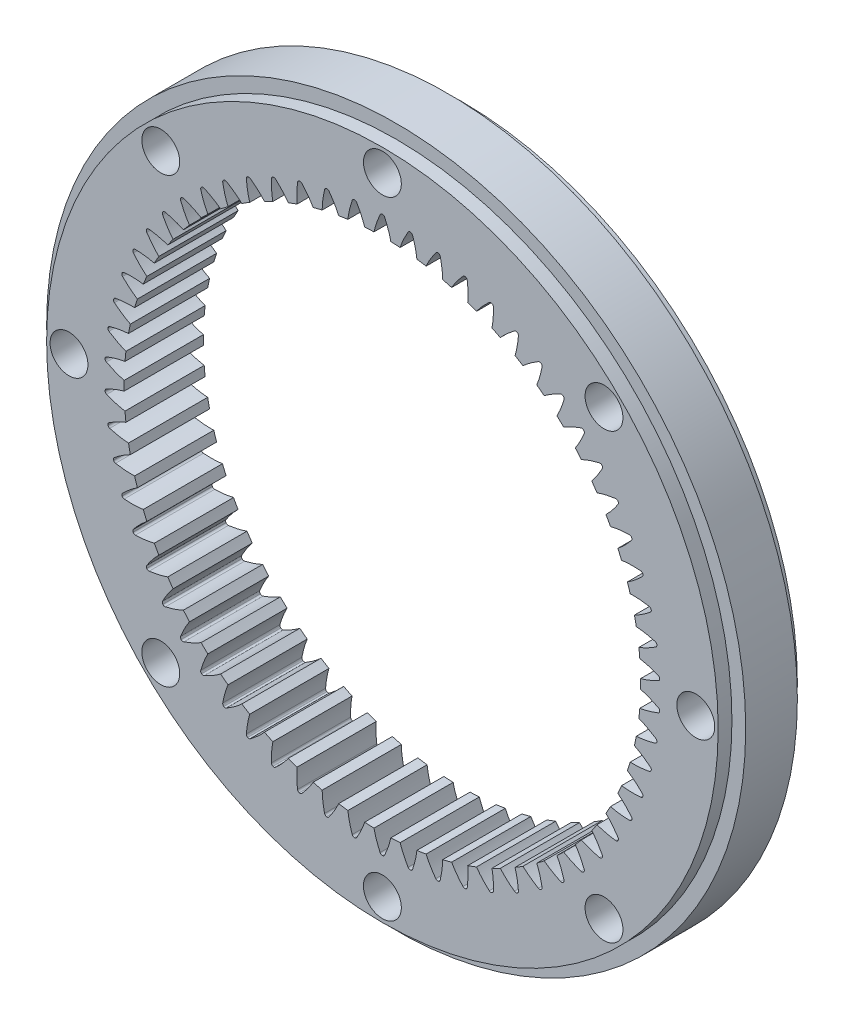
SolidWorks part; units mm, degrees
ref_plane "前视基准面" through (0, 0, 0) normal (0, 0, 1) x (1, 0, 0)
ref_plane "上视基准面" through (0, 0, 0) normal (0, 1, 0) x (1, 0, 0)
ref_plane "右视基准面" through (0, 0, 0) normal (1, 0, 0) x (0, 0, -1)
ref_axis "内齿轮基准轴" through (0, 0, -20.988) along (0, 0, 1)
sketch "草图1" plane through (0, 0, 0) normal (0, 0, 1) x (1, 0, 0)
  circle A0 centre (0, 0) radius 75
  circle A1 centre (0, 0) radius 101.5
extrude "凸台-拉伸1" add sketch "草图1" along normal blind 23
sketch "草图2" plane through (0, 0, 0) normal (0, 0, 1) x (1, 0, 0)
  circle A0 centre (0, 0) radius 75 construction
  arc A1 (2.4484, 74.96) -> (-2.4484, 74.96) centre (0, 0) ccw
  arc A2 (0.0188, 80.625) -> (-0.0188, 80.625) centre (0, 0) ccw
  arc A3 (0.6592, 80.2075) -> (0.0188, 80.625) centre (0.0187, 79.925) ccw
  arc A4 (-0.0188, 80.625) -> (-0.6592, 80.2075) centre (-0.0187, 79.925) ccw
  spline S0 degree 3 poles (-2.4484, 74.96) (-2.3488, 75.4313) (-2.0602, 76.5624) (-1.4785, 78.3226) (-0.9357, 79.5804) (-0.6592, 80.2075) knots 0.268524 0.268524 0.268524 0.268524 0.444446 0.694446 0.944634 0.944634 0.944634 0.944634
  spline S1 degree 3 poles (2.4484, 74.96) (2.3488, 75.4313) (2.0602, 76.5624) (1.4785, 78.3226) (0.9357, 79.5804) (0.6592, 80.2075) knots 0.268524 0.268524 0.268524 0.268524 0.444446 0.694446 0.944634 0.944634 0.944634 0.944634
  point P0 (-2.7265, 72.7751)
  point P1 (-2.723, 73.0033)
  point P2 (-2.6644, 73.6853)
  point P3 (-2.4791, 74.811)
  point P4 (-2.0971, 76.3619)
  point P5 (-1.4506, 78.311)
  point P6 (-0.475, 80.6236)
  dimension "D1" = 0.7
  dimension "D2" = 0.7
extrude "切除-拉伸1" cut sketch "草图2" against normal through all and the other way through all
pattern_circular "阵列(圆周)1" count 62 over 360 about axis through (0, 0, -20.988) along (0, 0, 1) of "切除-拉伸1"
sketch "草图3" plane through (0, 0, 0) normal (0, 0, 1) x (1, 0, 0)
  circle A0 centre (0, 91) radius 5.5
extrude "切除-拉伸2" cut sketch "草图3" against normal through all and the other way through all
pattern_circular "阵列(圆周)2" count 8 over 360 about axis through (0, 0, -20.988) along (0, 0, 1) of "切除-拉伸2"
ref_plane "BaseFace1" through (0, 0, 0) normal (0, 0, -1) x (-1, 0, 0)
ref_plane "BaseFace2" through (0, 0, 23) normal (0, 0, 1) x (1, 0, 0)
sketch "草图4" plane through (0, 0, 0) normal (0, 1, 0) x (1, 0, 0)
  line L0 (-101.5, -19) -> (-97.5, -19)
  line L1 (-101.5, 0) -> (-101.5, -23) construction
  line L2 (-97.5, -19) -> (-97.5, -23)
  line L3 (-101.5, -23) -> (101.5, -23) construction
  line L4 (-97.5, -23) -> (-101.5, -23)
  line L5 (-101.5, -23) -> (-101.5, -19)
  line L6 (0, 88.99) -> (0, -88.99) construction
  dimension "D1" = 4
  dimension "D2" = 97.5
revolve "切除-旋转1" cut sketch "草图4" angle 360 about axis through (0, 0, -20.988) along (0, 0, 1)
ref_plane "基准面1" through (0, 0, 11.5) normal (0, 0, -1) x (-1, 0, 0)
mirror "镜向1" about plane through (0, 0, 11.5) normal (0, 0, -1) of "切除-旋转1"
